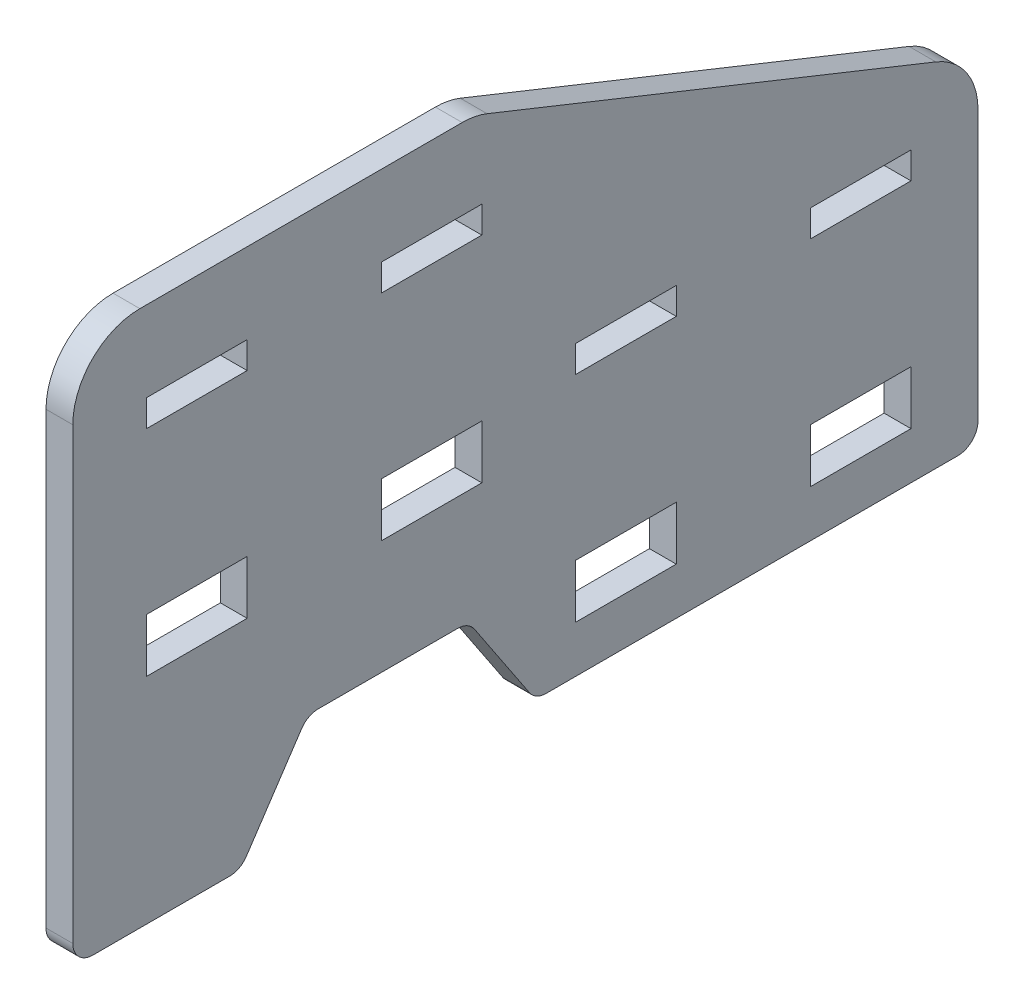
SolidWorks part; units mm, degrees
ref_plane "Front" through (0, 0, 0) normal (0, 0, 1) x (1, 0, 0)
ref_plane "Top" through (0, 0, 0) normal (0, 1, 0) x (1, 0, 0)
ref_plane "Right" through (0, 0, 0) normal (1, 0, 0) x (0, 0, -1)
sketch "Skizze1" plane through (0, 0, 0) normal (1, 0, 0) x (0, 0, -1)
  line L0 (0, 0) -> (25, 0)
  line L1 (25, 0) -> (35, 15)
  line L2 (35, 15) -> (59, 15)
  line L3 (59, 15) -> (69, 0)
  line L4 (69, 0) -> (135, 0)
  line L5 (135, 0) -> (135, 50)
  line L6 (135, 50) -> (60, 80)
  line L7 (60, 80) -> (0, 80)
  line L8 (0, 80) -> (0, 0)
  line L9 (35, 15) -> (25, 15) construction
  line L10 (25, 15) -> (25, 0) construction
  line L11 (59, 15) -> (69, 15) construction
  line L12 (69, 15) -> (69, 0) construction
  point P5 (47.5231, 15)
  dimension "D1" = 80
  dimension "135" = 135
  dimension "D3" = 66
  dimension "D4" = 15
  dimension "D5" = 10
  dimension "D6" = 60
  dimension "D7" = 50
  dimension "D8" = 25
extrude "Grundform" add sketch "Skizze1" along normal blind 4
sketch "Skizze2" plane through (4, 0, 0) normal (1, 0, 0) x (0, 0, -1)
  line L0 (90, 41) -> (110, 41) construction
  line L1 (75, 43) -> (90, 43)
  line L2 (75, 43) -> (75, 39)
  line L3 (75, 39) -> (90, 39)
  line L4 (90, 43) -> (90, 39)
  line L5 (100, 41) -> (100, 9) construction
  line L6 (100, 25) -> (141.5957, 25) construction
  line L7 (110, 43) -> (110, 39)
  line L8 (125, 39) -> (110, 39)
  line L9 (125, 43) -> (125, 39)
  line L10 (125, 43) -> (110, 43)
  line L11 (90, 9) -> (110, 9) construction
  line L12 (125, 7) -> (110, 7)
  line L13 (125, 7) -> (125, 11)
  line L14 (125, 11) -> (110, 11)
  line L15 (110, 7) -> (110, 11)
  line L16 (90, 7) -> (90, 11)
  line L17 (75, 11) -> (90, 11)
  line L18 (75, 7) -> (75, 11)
  line L19 (75, 7) -> (90, 7)
  line L20 (135, 0) -> (135, 50) construction
  line L21 (69, 0) -> (135, 0) construction
  line L22 (46, 66) -> (36, 66) construction
  line L39 (61, 68) -> (61, 64)
  line L56 (46, 68) -> (46, 64)
  line L57 (36, 66) -> (36, 34) construction
  line L58 (36, 50) -> (90.9252, 50) construction
  line L62 (26, 68) -> (26, 64)
  line L69 (11, 68) -> (11, 64)
  line L71 (11, 64) -> (26, 64)
  line L72 (11, 68) -> (26, 68)
  line L73 (61, 68) -> (46, 68)
  line L74 (61, 64) -> (46, 64)
  line L75 (46, 34) -> (36, 34) construction
  line L76 (36, 66) -> (26, 66) construction
  line L80 (11, 32) -> (26, 32)
  line L81 (11, 32) -> (11, 36)
  line L82 (11, 36) -> (26, 36)
  line L83 (26, 32) -> (26, 36)
  line L84 (46, 32) -> (46, 36)
  line L85 (61, 36) -> (46, 36)
  line L86 (61, 32) -> (61, 36)
  line L87 (61, 32) -> (46, 32)
  dimension "D1" = 4
  dimension "D2" = 15
  dimension "D3" = 20
  dimension "D4" = 32
  dimension "D5" = 35
  dimension "D6" = 25
  dimension "D7" = 64
  dimension "D8" = 25
  dimension "D9" = 20
extrude "Zapfendurchbruch" cut sketch "Skizze2" against normal through all
fillet "Verrundung1" radius 10 3 edges at (2, 80, 0) (2, 80, -60) (2, 50, -135)
fillet "Verrundung2" radius 3 6 edges at (2, 0, 0) (2, 0, -25) (2, 15, -35) (2, 15, -59) (2, 0, -69) (2, 0, -135)
sketch "Skizze3" plane through (0, 0, 0) normal (-1, 0, 0) x (0, 0, 1)
  line L0 (-125, 11) -> (-110, 11) construction
  line L1 (-125, 11) -> (-110, 11)
  line L2 (-125, 11) -> (-125, 15)
  line L3 (-125, 15) -> (-110, 15)
  line L4 (-110, 11) -> (-110, 15)
  line L5 (-90, 11) -> (-75, 11)
  line L6 (-90, 11) -> (-90, 15)
  line L7 (-90, 15) -> (-75, 15)
  line L8 (-75, 11) -> (-75, 15)
  line L9 (-61, 36) -> (-46, 36)
  line L10 (-61, 36) -> (-61, 40)
  line L11 (-61, 40) -> (-46, 40)
  line L12 (-46, 36) -> (-46, 40)
  line L13 (-26, 36) -> (-11, 36)
  line L14 (-26, 36) -> (-26, 40)
  line L15 (-26, 40) -> (-11, 40)
  line L16 (-11, 36) -> (-11, 40)
  line L17 (-125, 7) -> (-125, 11) construction
extrude "Zapfendurchbruch 2" cut sketch "Skizze3" against normal blind 4
